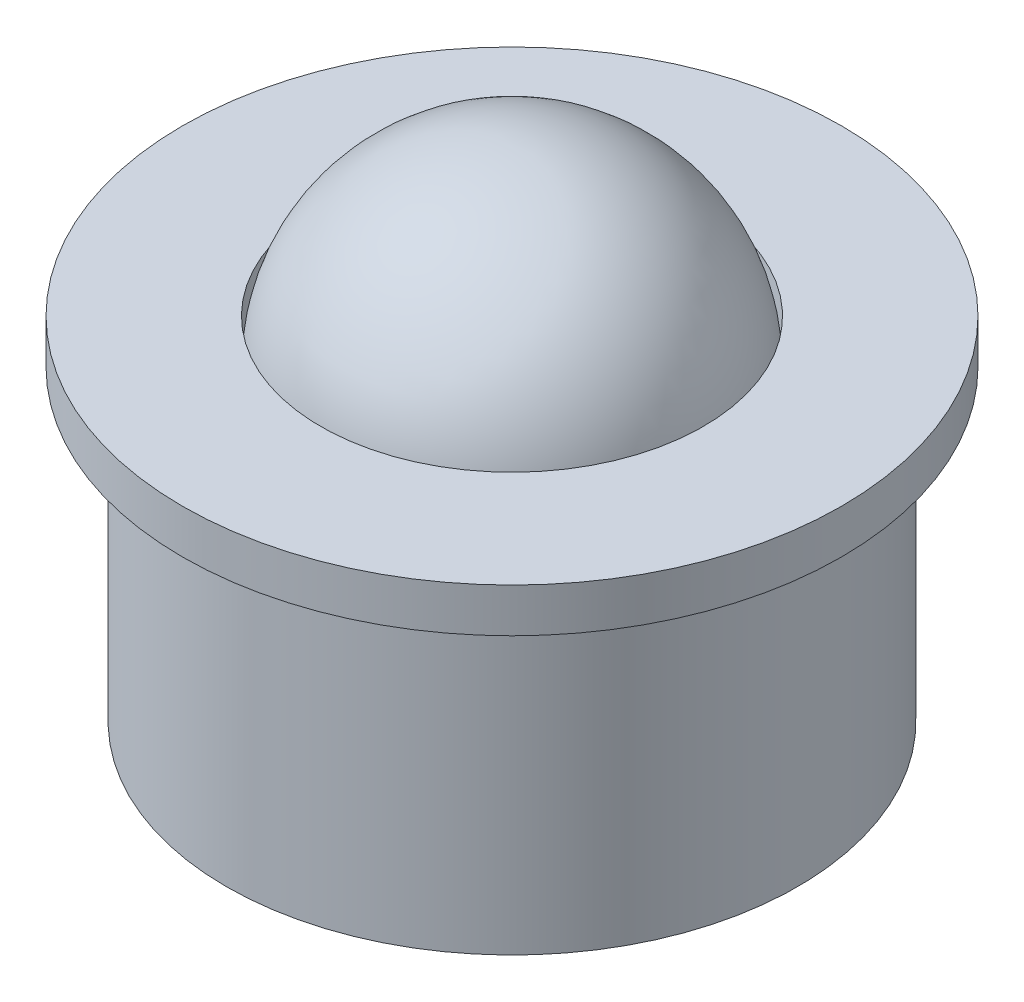
SolidWorks part; units mm, degrees
ref_plane "前视基准面" through (0, 0, 0) normal (0, 0, 1) x (1, 0, 0)
ref_plane "上视基准面" through (0, 0, 0) normal (0, 1, 0) x (1, 0, 0)
ref_plane "右视基准面" through (0, 0, 0) normal (1, 0, 0) x (0, 0, -1)
other "Configuration Table"
sketch "草图1" plane through (0, 0, 0) normal (0, 1, 0) x (1, 0, 0)
  line L0 (-4.355, 0) -> (4.355, 0)
  arc A0 (4.355, 0) -> (-4.355, 0) centre (0, 0) ccw
  dimension "D1" = 4.355
revolve "旋转1" add sketch "草图1" angle 180 about L0
sketch "草图5" plane through (0, 0, 0) normal (0, -1, 0) x (1, 0, 0)
  circle A0 centre (0, 0) radius 7.5
  circle A1 centre (0, 0) radius 6.5
  circle A2 centre (0, 0) radius 5.5
  circle M2 centre (0, 0) radius 4.355
  dimension "D1" = 15
  dimension "D2" = 13
  dimension "D3" = 11
extrude "凸台-拉伸1" add sketch "草图5" against normal blind 1 contours A1 M2 | A0 A1 | A2 M2 region at (-7.2879, 0, 0) region at (-6.3162, 0, 0) region at (-5.3444, 0, 0)
extrude "凸台-拉伸2" add sketch "草图5<4>" along normal blind 7 contours A1 A2 region at (-6.3162, 0, 0)
sketch "草图5<4>" plane through (0, 0, 0) normal (0, -1, 0) x (1, 0, 0) same geometry as "草图5"
